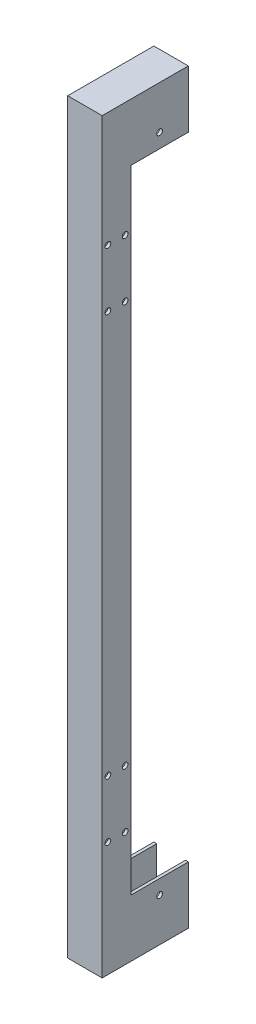
SolidWorks part; units mm, degrees
material "6061-T6 (SS)"
ref_plane "Front Plane" through (0, 0, 0) normal (1, 0, 0) x (0, 1, 0)
ref_plane "Top Plane" through (0, 0, 0) normal (0, 0, 1) x (0, 1, 0)
ref_plane "Right Plane" through (0, 0, 0) normal (0, 1, 0) x (-1, 0, 0)
sketch "Sketch1" plane through (0, 0, 0) normal (1, 0, 0) x (0, 1, 0)
  line L0 (-7247.7074, 0) -> (355137.6648, 0) construction
  line L1 (0, -7247.7074) -> (0, 355137.6648) construction
  line L2 (550, -125) -> (650, -125)
  line L3 (-550, 25) -> (550, 25)
  line L5 (-550, -25) -> (550, -25)
  line L7 (-550, 25) -> (550, -25) construction
  line L8 (-550, -25) -> (550, 25) construction
  line L9 (-550, 25) -> (-650, 25)
  line L10 (-550, -25) -> (-550, -125)
  line L11 (-550, -125) -> (-650, -125)
  line L12 (-650, 25) -> (-650, -125)
  line L13 (650, 25) -> (650, -125)
  line L14 (550, 25) -> (650, 25)
  line L16 (550, -25) -> (550, -125)
  point P4 (0, 0)
  dimension "D1" = 1100
  dimension "D2" = 50
  dimension "D3" = 100
  dimension "D4" = 150
extrude "Boss-Extrude1" add sketch "Sketch1" along normal mid plane 60 contours L5 L16 L2 L13 L14 L3 L9 L12 L11 L10 region at (0, 0, -17.6471)
shell "Shell1" thickness 5 removed face at (0, 600, -125) removed face at (0, -600, -125) removed face at (0, -550, -75) removed face at (0, 550, -75)
sketch "Sketch2" plane through (30, 0, 0) normal (1, 0, 0) x (0, 1, 0)
  line L0 (-575, -1065.5759) -> (-575, 48934.4241) construction
  line L2 (-550, -25) -> (-550, -125) construction
  line L4 (0, -1000) -> (0, 49000) construction
  circle A0 centre (-575, -75) radius 5
  circle A1 centre (575, -75) radius 5
  point P9 (-550, -75)
  dimension "D2" = 10
  dimension "D1" = 25
extrude "Cut-Extrude1" cut sketch "Sketch2" against normal through all contours A0 | A1 | A0 region at (30, -575, -75) region at (30, 575, -75)
sketch "Sketch3" plane through (30, 0, 0) normal (1, 0, 0) x (0, 1, 0)
  line L0 (-1000, 0) -> (49000, 0) construction
  line L1 (-400, -999.5892) -> (-400, 49000.4108) construction
  line L2 (-550, -25) -> (-550, -125) construction
  line L3 (0, -55) -> (0, 55) construction
  circle A0 centre (-350, 15) radius 5
  circle A1 centre (-350, -15) radius 5
  circle A2 centre (-450, 15) radius 5
  circle A3 centre (-450, -15) radius 5
  circle A4 centre (450, -15) radius 5
  circle A5 centre (450, 15) radius 5
  circle A6 centre (350, -15) radius 5
  circle A7 centre (350, 15) radius 5
  dimension "D3" = 10
  dimension "D1" = 50
  dimension "D2" = 15
  dimension "D4" = 150
extrude "Cut-Extrude2" cut sketch "Sketch3" against normal up to next
